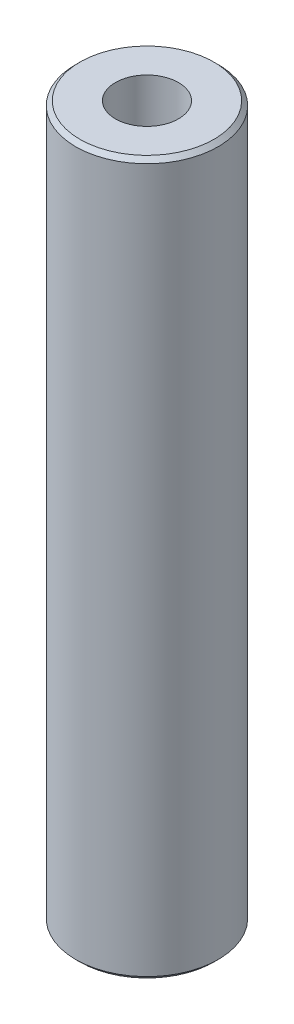
SolidWorks part; units mm, degrees
ref_plane "Front Plane" through (0, 0, 0) normal (0, 0, 1) x (1, 0, 0)
ref_plane "Top Plane" through (0, 0, 0) normal (0, 1, 0) x (1, 0, 0)
ref_plane "Right Plane" through (0, 0, 0) normal (1, 0, 0) x (0, 0, -1)
sketch "Sketch1" plane through (0, 0, 0) normal (0, 1, 0) x (1, 0, 0)
  circle A0 centre (0, 0) radius 60
  dimension "SHAFT_OD" = 120
extrude "Boss-Extrude1" add sketch "Sketch1" along normal blind 600
sketch "Sketch2" plane through (0, 0, 0) normal (0, 1, 0) x (1, 0, 0)
  circle A0 centre (0, 0) radius 26.555
  dimension "BORE_D" = 53.1099
extrude "Cut-Extrude1" cut sketch "Sketch2" along normal through all
chamfer "Chamfer1" distance 3.5866 angle 45 2 edges at (0, 600, 60) (0, 0, 60)
